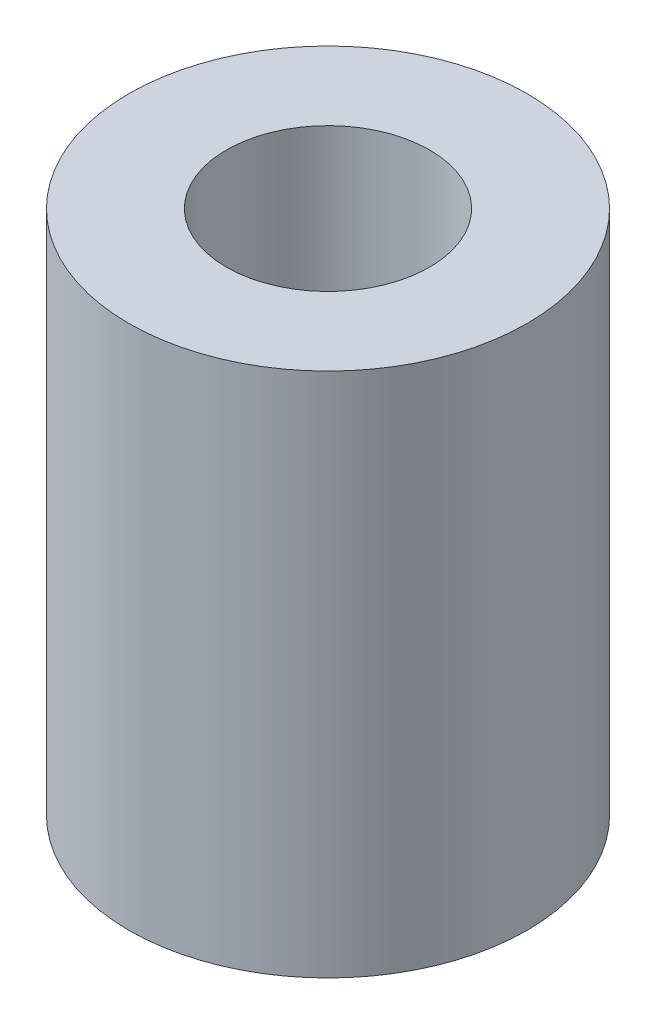
SolidWorks part; units mm, degrees
ref_plane "Front Plane" through (0, 0, 0) normal (0, 0, 1) x (1, 0, 0)
ref_plane "Top Plane" through (0, 0, 0) normal (0, 1, 0) x (1, 0, 0)
ref_plane "Right Plane" through (0, 0, 0) normal (1, 0, 0) x (0, 0, -1)
sketch "Sketch1" plane through (0, 0, 0) normal (0, 1, 0) x (1, 0, 0)
  circle A0 centre (0, 0) radius 7.9375
  dimension "D1" = 15.875
extrude "Boss-Extrude1" add sketch "Sketch1" along normal blind 20.955
sketch "Sketch2" plane through (0, 20.955, 0) normal (0, 1, 0) x (1, 0, 0)
  circle A0 centre (0, 0) radius 4
  dimension "D1" = 8
sketch "Sketch3" plane through (0, 20.955, 0) normal (0, 1, 0) x (1, 0, 0)
  circle A0 centre (0, 0) radius 4.05
  dimension "D1" = 8.1
extrude "Cut-Extrude2" cut sketch "Sketch3" against normal through all
